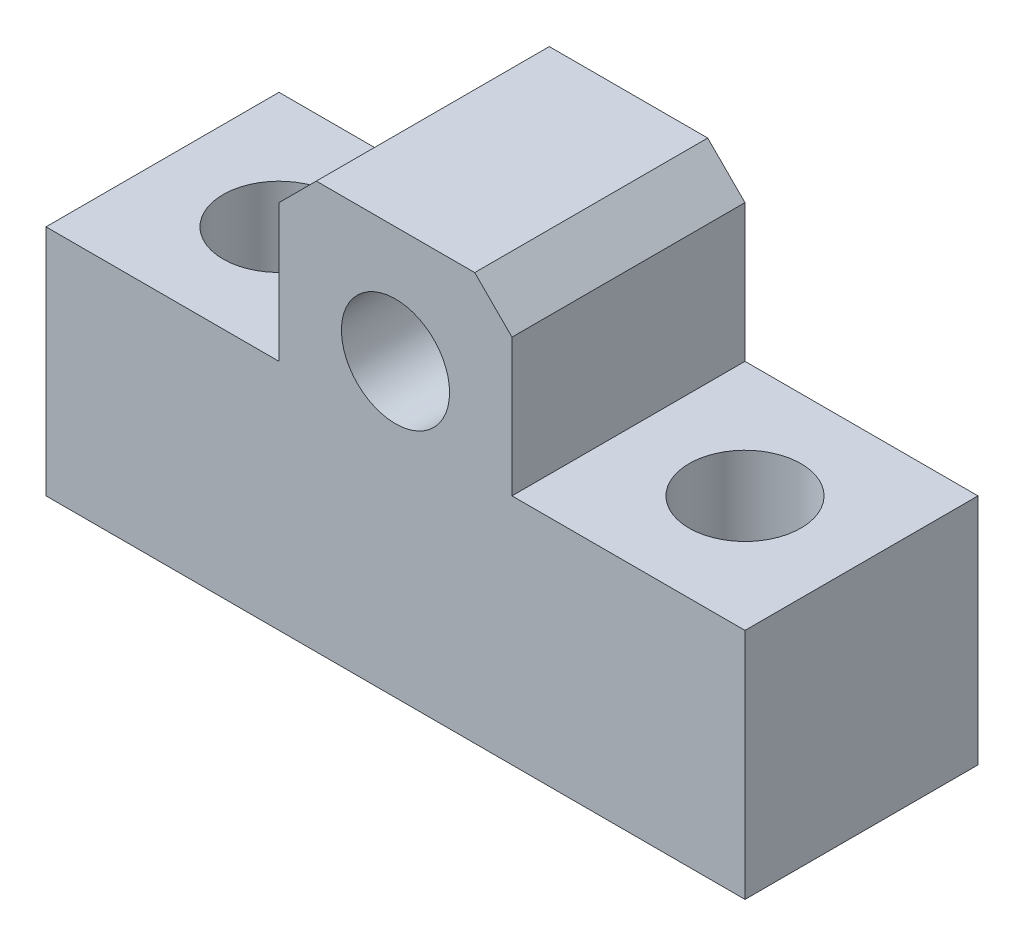
SolidWorks part; units mm, degrees
material "6061-T6 (SS)"
ref_plane "Front Plane" through (0, 0, 0) normal (0, 0, 1) x (1, 0, 0)
ref_plane "Top Plane" through (0, 0, 0) normal (0, 1, 0) x (1, 0, 0)
ref_plane "Right Plane" through (0, 0, 0) normal (1, 0, 0) x (0, 0, -1)
sketch "Sketch1" plane through (0, 0, 0) normal (0, 0, 1) x (1, 0, 0)
  line L0 (-9.525, 3.175) -> (9.525, -3.175) construction
  line L1 (-9.525, 3.175) -> (9.525, 3.175)
  line L2 (-9.525, 3.175) -> (-9.525, -3.175)
  line L3 (-9.525, -3.175) -> (9.525, -3.175)
  line L4 (9.525, 3.175) -> (9.525, -3.175)
  point P4 (0, 0)
  dimension "D1" = 19.05
  dimension "D2" = 6.35
extrude "Boss-Extrude1" add sketch "Sketch1" along normal blind 6.35
sketch "Sketch6" plane through (0, 3.175, 0) normal (0, 1, 0) x (1, 0, 0)
  line L0 (9.525, 0) -> (-9.525, 0) construction
  line L1 (3.175, 0) -> (-3.175, 0)
  line L2 (3.175, 0) -> (3.175, -6.35)
  line L3 (3.175, -6.35) -> (-3.175, -6.35)
  line L4 (-3.175, 0) -> (-3.175, -6.35)
  line L5 (9.525, -6.35) -> (-9.525, -6.35) construction
  point P8 (0, 0)
  point P9 (0, 0)
  dimension "D1" = 6.35
extrude "Boss-Extrude2" add sketch "Sketch6" along normal blind 4.7625
hole_wizard "Tapped Hole for #4-40 Helicoil1" positions "Sketch2" profile "Sketch3" tap size "#4-40" standard "Helicoil® Inch" end condition through all
sketch "Sketch2" plane through (0, 3.175, 0) normal (0, 1, 0) x (1, 0, 0)
  line L0 (0, 0) -> (0, -6.35) construction
  line L4 (-9.525, -6.35) -> (-9.525, 0) construction
  line L5 (-9.525, -6.35) -> (9.525, -6.35) construction
  line L6 (-9.525, 0) -> (9.525, 0) construction
  point P0 (-6.35, -3.175)
  point P13 (6.35, -3.175)
  point P16 (0, -3.175)
  dimension "D1" = 3.175
sketch "Sketch3" plane through (-6.35, 3.175, 3.175) normal (1, 0, 0) x (0, 0, 1)
  line L0 (0, 0) -> (0, 6.35)
  line L1 (0, 6.35) -> (1.524, 6.35)
  line L2 (1.524, 6.35) -> (1.524, 0)
  line L5 (1.524, 0) -> (0, 0)
  line L11 (0, -6.35) -> (0, 107.95) construction
  dimension "Thru Tap Drill Dia." = 3.048
  dimension "Thru Tap Drill Depth" = 6.35
cosmetic thread "Hole Thread1" parameters "D1"=6.35, "D2"=3.7414
cosmetic thread "Hole Thread2" parameters "D1"=6.35, "D2"=3.7414
hole_wizard "#4 Clearance Hole1" positions "Sketch4" profile "Sketch5" hole size "#4" standard "ANSI Inch" end condition through all
sketch "Sketch4" plane through (0, 0, 6.35) normal (0, 0, 1) x (1, 0, 0)
  line L6 (-3.175, 4.7625) -> (0, 4.7625) construction
  line L7 (-3.175, 7.9375) -> (-3.175, 3.175) construction
  line L8 (0, 4.7625) -> (0, 7.9375) construction
  line L9 (-3.175, 7.9375) -> (3.175, 7.9375) construction
  point P0 (0, 4.7625)
sketch "Sketch5" plane through (0, 4.7625, 6.35) normal (1, 0, 0) x (0, -1, 0)
  line L0 (0, 0) -> (0, 6.35)
  line L1 (0, 6.35) -> (1.4732, 6.35)
  line L2 (1.4732, 6.35) -> (1.4732, 0)
  line L5 (1.4732, 0) -> (0, 0)
  line L11 (0, -6.35) -> (0, 107.95) construction
  dimension "Thru Hole Dia." = 2.9464
  dimension "Thru Hole Depth" = 6.35
chamfer "distinguishingMark" distance 1.016 angle 45 2 edges at (3.175, 7.9375, 3.175) (-3.175, 7.9375, 3.175)
